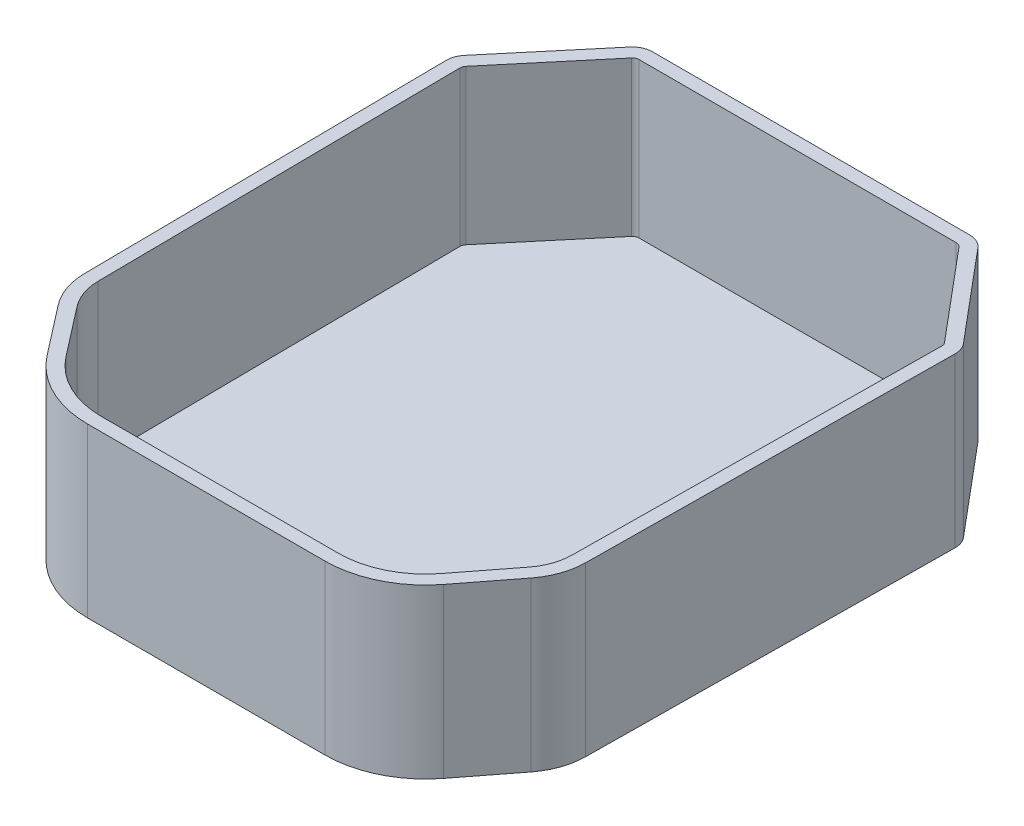
SolidWorks part; units mm, degrees
ref_plane "Ebene vorne" through (0, 0, 0) normal (0, 0, 1) x (1, 0, 0)
ref_plane "Ebene oben" through (0, 0, 0) normal (0, 1, 0) x (1, 0, 0)
ref_plane "Ebene rechts" through (0, 0, 0) normal (1, 0, 0) x (0, 0, -1)
sketch "Skizze1" plane through (0, 0, 0) normal (0, 1, 0) x (1, 0, 0)
  line L0 (-71.7828, 0) -> (65.2574, 0) construction
  line L1 (-55, 0) -> (55, 0) construction
  line L2 (0, 50.8602) -> (0, -44.8504) construction
  line L3 (0, -55) -> (0, 55) construction
  line L4 (0, -50.1714) -> (-25, -50.1714)
  line L5 (-25, -50.1714) -> (-37.2443, -34.3575)
  line L6 (-37.2443, -34.3575) -> (-37.8558, 24.5078)
  line L7 (-37.8558, 24.5078) -> (-25, 39.8286)
  line L8 (-25, 39.8286) -> (0, 39.8286)
  line L9 (0, 39.8286) -> (0, -50.1714)
  dimension "D1" = 25
  dimension "D2" = 130
  dimension "D3" = 20
  dimension "D4" = 90
extrude "Aufsatz-Linear austragen1" add sketch "Skizze1" along normal blind 25
mirror "Spiegeln1" about plane through (0, 0, 0) normal (1, 0, 0) of "Aufsatz-Linear austragen1"
fillet "Verrundung11" radius 15 2 edges at (-25, 12.5, 50.1714) (25, 12.5, 50.1714)
fillet "Verrundung12" radius 10 2 edges at (37.2443, 12.5, 34.3575) (-37.2443, 12.5, 34.3575)
fillet "Verrundung13" radius 3 2 edges at (-25, 12.5, -39.8286) (25, 12.5, -39.8286)
fillet "Verrundung14" radius 3 2 edges at (37.8558, 12.5, -24.5078) (-37.8558, 12.5, -24.5078)
shell "Wandung4" thickness 2 removed face at (0, 25, 4.5532)
